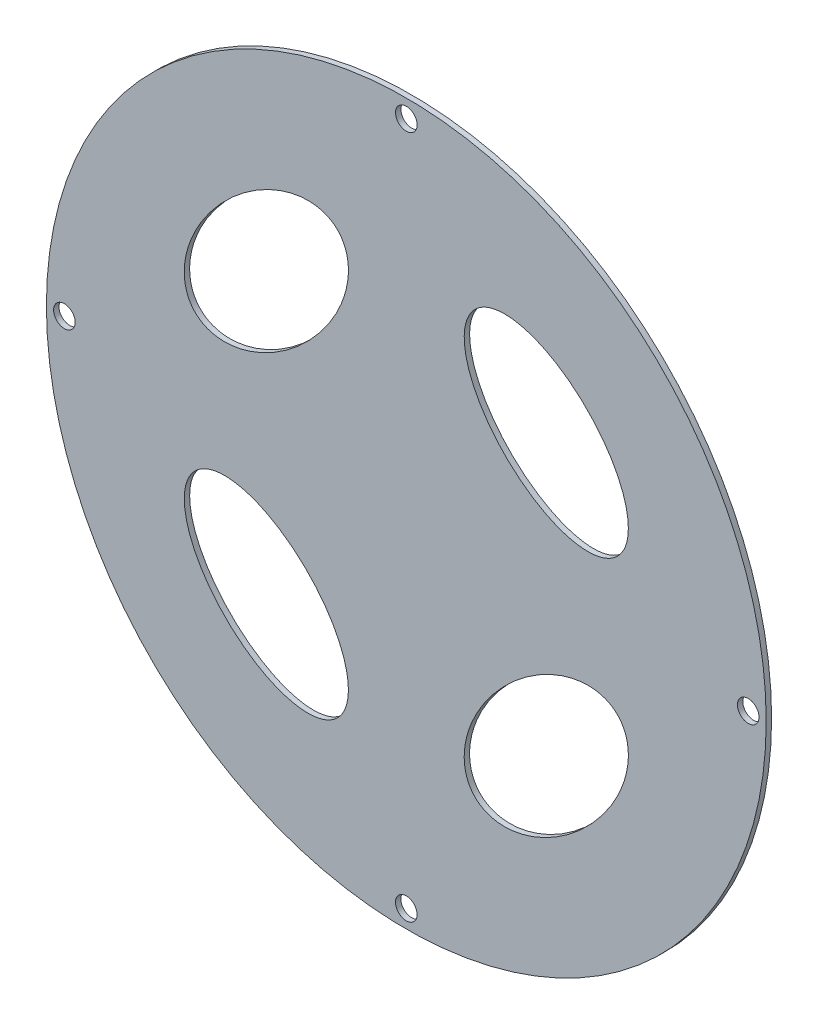
SolidWorks part; units mm, degrees
ref_plane "Front Plane" through (0, 0, 0) normal (0, 0, 1) x (1, 0, 0)
ref_plane "Top Plane" through (0, 0, 0) normal (0, 1, 0) x (1, 0, 0)
ref_plane "Right Plane" through (0, 0, 0) normal (1, 0, 0) x (0, 0, -1)
sketch "Sketch1" plane through (0, 0, 0) normal (0, 0, 1) x (1, 0, 0)
  circle A0 centre (0, 0) radius 100
  dimension "D1" = 200
extrude "Base Disc" add sketch "Sketch1" along normal blind 1.5
sketch "Sketch2" plane through (0, 0, 0) normal (0, 0, -1) x (-1, 0, 0)
  circle A0 centre (0, 0) radius 20
  circle A1 centre (0, 0) radius 3
extrude "Boss-Extrude2" add sketch "Sketch2" along normal blind 8
sketch "Sketch3" plane through (0, 0, 0) normal (0, 0, -1) x (-1, 0, 0)
  circle A0 centre (95, 0) radius 3
extrude "Cut-Extrude1" cut sketch "Sketch3" against normal through all
pattern_circular "CirPattern1" count 4 over 360 about axis through (0, 0, 0) along (0, 0, -1) of "Cut-Extrude1"
sketch "Sketch4" plane through (0, 0, 0) normal (0, 0, -1) x (-1, 0, 0)
  line L0 (0, 0) -> (38.8909, 38.8909) construction
  ellipse E0 centre (38.8909, 38.8909) end of major axis (19.0919, 58.6899) minor radius 16
extrude "Cut-Extrude2" cut sketch "Sketch4" against normal through all
pattern_circular "CirPattern2" count 4 over 360 about axis through (0, 0, -8) along (0, 0, -1) of "Cut-Extrude2"
